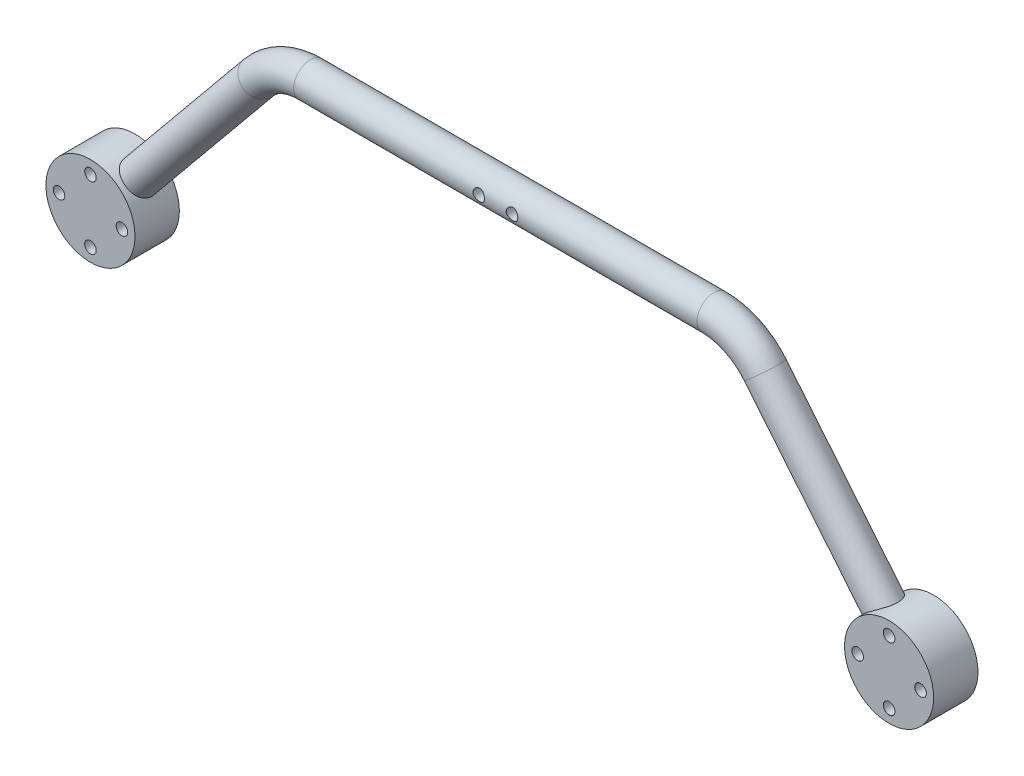
SolidWorks part; units mm, degrees
ref_plane "Front Plane" through (0, 0, 0) normal (0, 0, 1) x (1, 0, 0)
ref_plane "Top Plane" through (0, 0, 0) normal (0, 1, 0) x (1, 0, 0)
ref_plane "Right Plane" through (0, 0, 0) normal (1, 0, 0) x (0, 0, -1)
sketch "Sketch1" plane through (0, 0, 0) normal (0, 0, 1) x (1, 0, 0)
  line L0 (-216.0578, -96.9368) -> (-12.9419, -12.8035)
  line L1 (-216.0578, -96.9368) -> (-206.3377, -120.4034)
  line L2 (-12.9419, -12.8035) -> (-3.2218, -36.27)
  line L3 (-206.3377, -120.4034) -> (-3.2218, -36.27)
  line L4 (12.9419, -12.8035) -> (216.0578, -96.9368)
  line L5 (12.9419, -12.8035) -> (3.2218, -36.27)
  line L6 (216.0578, -96.9368) -> (206.3377, -120.4034)
  line L7 (3.2218, -36.27) -> (206.3377, -120.4034)
  line L8 (-12.9419, -12.8035) -> (0, -7.4427)
  line L9 (0, -7.4427) -> (12.9419, -12.8035)
  line L10 (0, 19.4566) -> (0, -8.1997) construction
  line L11 (-228.6, -115.5981) -> (-228.6, -90.0981) construction
  line L12 (228.6, -115.5981) -> (228.6, -90.0981) construction
  circle A0 centre (-228.6, -115.5981) radius 25.5
  circle A3 centre (-228.6, -115.5981) radius 85.471 construction
  circle A4 centre (228.6, -115.5981) radius 25.5
  circle A5 centre (228.6, -115.5981) radius 85.471 construction
  point P16 (-228.6, -97.5981)
  point P17 (228.6, -97.5981)
  dimension "D5" = 51
  dimension "D6" = 170.942
  dimension "D1" = 135
  dimension "D2" = 25.4
  dimension "D3" = 25.4
  dimension "D4" = 18
  dimension "D7" = 18
  dimension "D8" = 457.2
extrude "Boss-Extrude1" add sketch "Sketch1" along normal blind 25.4 contours L0 A0 L3 L1 | L4 A4 L7 L6 | L3 A0 L0 L1 | L7 A4 L4 L6 region at (-230.1225, -116.2161, 0) region at (-208.5356, -107.4543, 0) region at (230.1225, -116.2161, 0) region at (208.5356, -107.4543, 0)
hole_wizard "M6 Clearance Hole1" positions "3DSketch2" profile "Sketch3" hole size "M6" standard "ANSI Metric" end condition through all
sketch3d "3DSketch2"
  point P2 (-228.6, -97.5981, 0)
sketch "Sketch3" plane through (-228.6, -97.5981, 0) normal (1, 0, 0) x (0, 1, 0)
  line L0 (0, 0) -> (0, 25.4)
  line L1 (0, 25.4) -> (3.3, 25.4)
  line L2 (3.3, 25.4) -> (3.3, 0)
  line L5 (3.3, 0) -> (0, 0)
  line L11 (0, -6.35) -> (0, 107.95) construction
  dimension "Thru Hole Dia." = 6.6
  dimension "Thru Hole Depth" = 25.4
sketch "Sketch26" plane through (0, 0, 25.4) normal (0, 0, 1) x (1, 0, 0)
  point P0 (228.6, -97.5981)
hole_wizard "M6 Clearance Hole3" positions "Sketch26" profile "Sketch27" hole size "M6" standard "ANSI Metric" end condition through all
sketch "Sketch27" plane through (228.6, -97.5981, 25.4) normal (1, 0, 0) x (0, -1, 0)
  line L0 (0, 0) -> (0, 25.4)
  line L1 (0, 25.4) -> (3.3, 25.4)
  line L2 (3.3, 25.4) -> (3.3, 0.025)
  line L3 (3.3, 0.025) -> (3.325, 0)
  line L5 (3.325, 0) -> (0, 0)
  line L6 (-3.3, 0.025) -> (-3.325, 0) construction
  line L11 (0, -6.35) -> (0, 107.95) construction
  dimension "Thru Hole Dia." = 6.6
  dimension "Thru Hole Depth" = 25.4
  dimension "Near C'Sink Dia." = 6.65
  dimension "Near C'Sink Angle" = 90
pattern_circular "CirPattern1" count 4 over 360 about axis through (-228.6, -115.5981, 25.4) along (0, 0, -1) of "M6 Clearance Hole1"
pattern_circular "CirPattern2" count 4 over 360 about axis through (228.6, -115.5981, 25.4) along (0, 0, -1) of "M6 Clearance Hole3"
ref_plane "Plane1" through (0, 0, 12.7) normal (0, 0, 1) x (1, 0, 0)
sketch "Sketch4" plane through (0, 0, 12.7) normal (0, 0, 1) x (1, 0, 0)
  line L0 (-218.4565, -103.4806) -> (-144.8982, -13.9185)
  line L1 (-115.4556, 0) -> (115.4556, 0)
  line L2 (144.8982, -13.9185) -> (218.4565, -103.4806)
  arc A0 (115.4556, 0) -> (144.8982, -13.9185) centre (115.4556, -38.1) cw
  arc A1 (-144.8982, -13.9185) -> (-115.4556, 0) centre (-115.4556, -38.1) cw
  dimension "D1" = 38.1
sweep "Sweep1" add path "Sketch4" circular profile diameter 19.05 parameters "D3"=19.05
sketch "Sketch23" plane through (0, 0, 25.4) normal (0, 0, 1) x (1, 0, 0)
  line L0 (-9.525, 0) -> (9.525, 0) construction
  dimension "D1" = 19.05
hole_wizard "M6 Clearance Hole2" positions "3DSketch3" profile "Sketch25" hole size "M6" standard "ANSI Metric" end condition through all
sketch3d "3DSketch3"
  point P0 (-9.525, 0, 22.225)
  point P2 (9.525, 0, 22.225)
sketch "Sketch25" plane through (-9.525, 0, 22.225) normal (1, 0, 0) x (0, -1, 0)
  line L0 (0, 0) -> (0, 22.225)
  line L1 (0, 22.225) -> (3.3, 22.225)
  line L2 (3.3, 22.225) -> (3.3, 0.025)
  line L3 (3.3, 0.025) -> (3.325, 0)
  line L5 (3.325, 0) -> (0, 0)
  line L6 (-3.3, 0.025) -> (-3.325, 0) construction
  line L11 (0, -6.35) -> (0, 107.95) construction
  dimension "Thru Hole Dia." = 6.6
  dimension "Thru Hole Depth" = 22.225
  dimension "Near C'Sink Dia." = 6.65
  dimension "Near C'Sink Angle" = 90
equation "\"Rover_Length\"= 25in"
equation "\"Rover_Width\"= 18in"
equation "\"Rover_Height\"= 12in"
equation "\"Chassis_Wheelbase\"= 18in"
equation "\"Chassis_WheelDiam\"= 171mm"
equation "\"Chassis_ArmDiamWidth\"= 0.75in"
equation "\"Chassis_ArmAngle\"= 135deg"
equation "\"Chassis_HubMountOD\"= \"Chassis_WheelBoltHole\" + 3mm + 12mm"
equation "\"Chassis_WheelBoltHole\"= 36mm"
equation "\"Chassis_WheelBoltNum\"= 4"
equation "\"Chassis_DiffBarLength\"= 12in"
equation "\"Chassis_DiffBarWidth\"= 1in"
equation "\"Chassis_DiffBarHeight\"= 0.5in"
equation "\"Chassis_DiffLinkage_Length\"= 2.5in"
equation "\"D2@Sketch1\"=\"Chassis_DiffBarWidth\""
equation "\"D3@Sketch1\"=\"Chassis_DiffBarWidth\""
equation "\"D5@Sketch1\"=\"Chassis_HubMountOD\""
equation "\"D4@Sketch1\"=\"Chassis_WheelBoltHole\"/2"
equation "\"D7@Sketch1\"=\"Chassis_WheelBoltHole\"/2"
equation "\"D8@Sketch1\"=\"Chassis_Wheelbase\""
equation "\"D1@Boss-Extrude1\"=\"Chassis_DiffBarWidth\""
